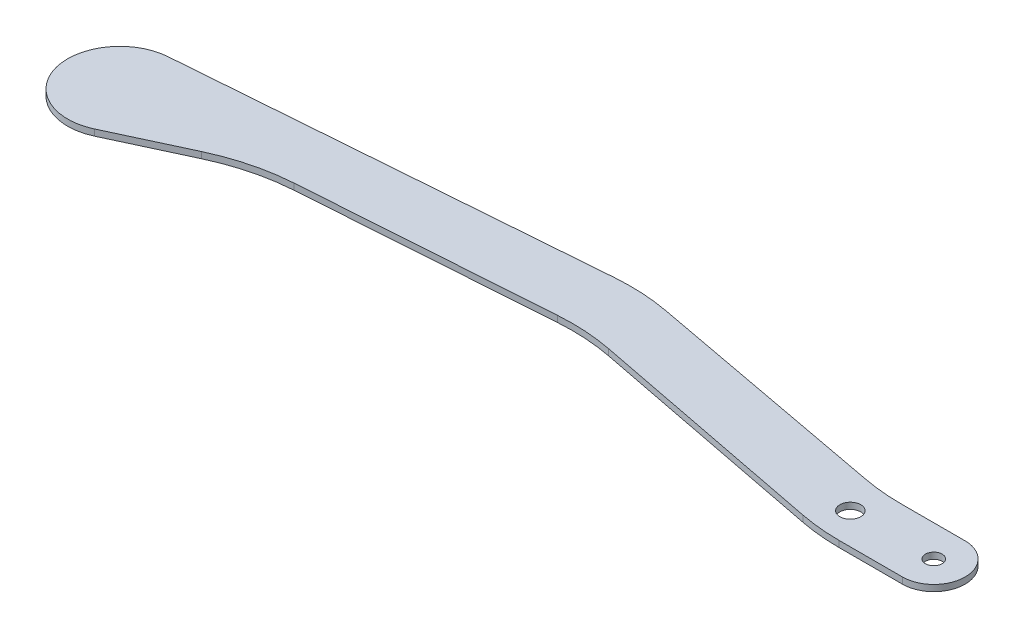
SolidWorks part; units mm, degrees
ref_plane "Front Plane" through (0, 0, 0) normal (0, 0, 1) x (1, 0, 0)
ref_plane "Top Plane" through (0, 0, 0) normal (0, 1, 0) x (1, 0, 0)
ref_plane "Right Plane" through (0, 0, 0) normal (1, 0, 0) x (0, 0, -1)
sketch "Sketch1" plane through (0, 0, 0) normal (0, 1, 0) x (1, 0, 0)
  line L0 (0, 0) -> (-350, 0) construction
  line L1 (0, 0) -> (40, 0) construction
  line L2 (0, 15) -> (40, 15)
  line L3 (0, -15) -> (40, -15)
  line L4 (-351.9193, 24.9262) -> (-339.4626, -22.6708) construction
  line L5 (-140.1953, 41.229) -> (-4213.5497, -272.4198)
  line L6 (0, 15) -> (-4015.3501, 766.2279)
  line L7 (0, 15) -> (-5.5236, -13.946) construction
  line L8 (-4213.5497, -272.4198) -> (-138.0387, 11.8369)
  line L9 (-4015.3501, 766.2279) -> (-5.5236, -13.946)
  line L10 (-339.4626, -22.6708) -> (-287.6751, 1.4001)
  line L11 (-5.5236, -13.946) -> (0, -15)
  circle A0 centre (0, 0) radius 5
  circle A1 centre (-350, 0) radius 25
  circle A2 centre (40, 0) radius 4
  circle A3 centre (0, 0) radius 15
  circle A4 centre (40, 0) radius 15
  point P17 (-125.6196, 9.6772)
  point P20 (-112.2232, 37.5108)
  point P21 (-246.7321, 0)
  point P22 (-242.6493, 2.9815)
  point P23 (-135.7072, 15)
  point P24 (-278.6267, 12.0678)
  point P25 (-135.3475, 11.5979)
  dimension "D1" = 10
  dimension "D4" = 8
  dimension "D5" = 50
  dimension "D6" = 30
  dimension "D7" = 165
  dimension "D2" = 350
  dimension "D3" = 40
  dimension "D8" = 165
  dimension "D9" = 135
  dimension "D10" = 150
extrude "Boss-Extrude1" add sketch "Sketch1" along normal blind 3 contours L8 A1 | A1 L8 | A1 L8 L9 L5 | A1 L10 L8 | A3 L6 L5 L9 | A3 A0 | A4 L2 A3 L3 | A4 A2 region at (-104.638, 0, -18.6726) region at (20, 0, 0) region at (10.3066, 0, -10.3066) region at (50.3066, 0, -10.3066) region at (-257.8424, 0, -16.1966) region at (-350.629, 0, -9.0187) region at (-314.6869, 0, 6.4517) region at (-349.15, 0, 12.1861)
fillet "Fillet1" radius 100 5 edges at (0, 1.5, -15) (-140.1953, 1.5, -41.229) (-138.0387, 1.5, -11.8369) (-287.6751, 1.5, -1.4001) (0, 1.5, 15)
